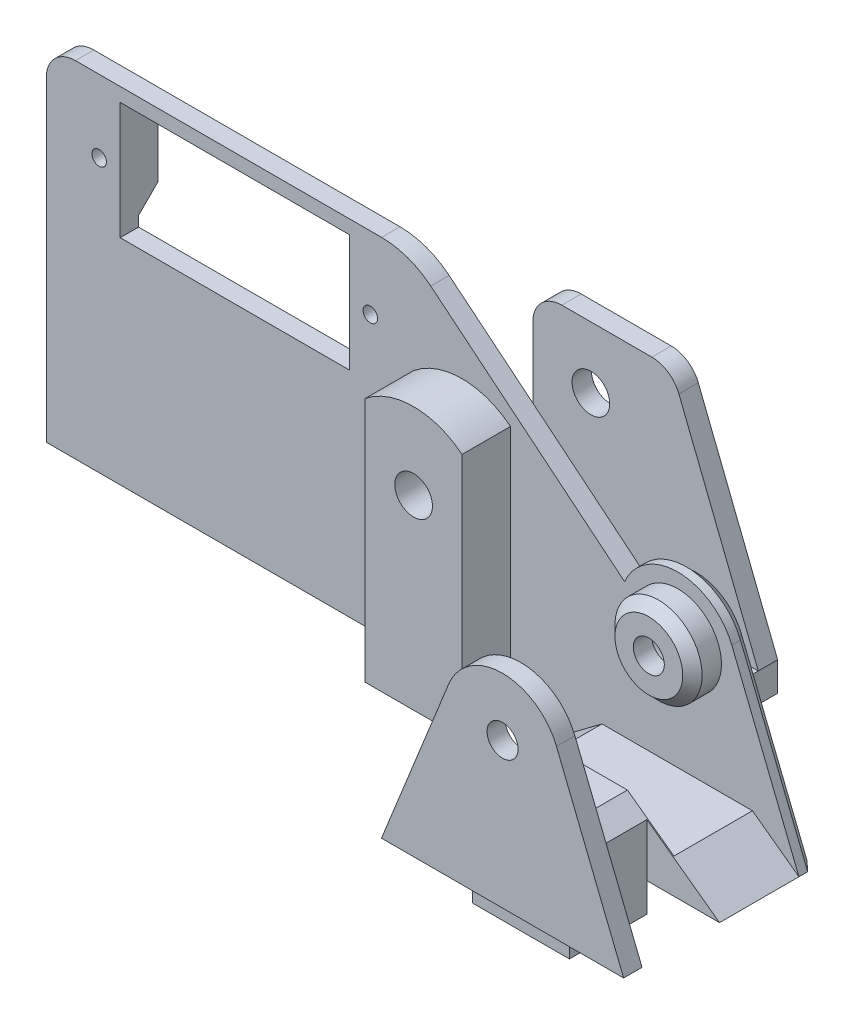
SolidWorks part; units mm, degrees
ref_plane "Alzado" through (0, 0, 0) normal (0, 0, 1) x (1, 0, 0)
ref_plane "Planta" through (0, 0, 0) normal (0, 1, 0) x (1, 0, 0)
ref_plane "Vista lateral" through (0, 0, 0) normal (1, 0, 0) x (0, 0, -1)
sketch "Croquis1" plane through (0, 0, 0) normal (0, 0, 1) x (1, 0, 0)
  line L0 (-12.5, -15) -> (-5.5666, 2.2389)
  line L1 (5.5666, 2.2389) -> (12.5, -15)
  line L2 (12.5, -15) -> (-12.5, -15)
  line L3 (0, 0) -> (0, -50000) construction
  circle A0 centre (0, 0) radius 1.6
  arc A1 (-5.5666, 2.2389) -> (5.5666, 2.2389) centre (0, 0) cw
  point P7 (0, -15)
  dimension "D1" = 3.2
  dimension "D2" = 6
  dimension "D3" = 15
  dimension "D4" = 25
extrude "Saliente-Extruir1" add sketch "Croquis1" along normal mid plane 20
sketch "Croquis2" plane through (0, 0, 0) normal (0, 0, 1) x (1, 0, 0)
  line L0 (12.5, -15) -> (5.5666, 2.2389) construction
  line L1 (-12.5, -15) -> (-7.5, 0)
  line L2 (12.5, -15) -> (7.5, 0)
  line L5 (-5.5666, 2.2389) -> (-12.5, -15) construction
  line L6 (-12.5, -15) -> (12.5, -15) construction
  line L7 (-12.5, -15) -> (-3.1648, -8)
  line L8 (-3.1648, -8) -> (2.8886, -8)
  line L9 (2.8886, -8) -> (12.5, -15)
  arc A0 (7.5, 0) -> (-7.5, 0) centre (0, 0) ccw
  dimension "D1" = 15
  dimension "D2" = 8
extrude "Cortar-Extruir1" cut sketch "Croquis2" against normal blind 8.1 and the other way blind 8.1
sketch "Croquis3" plane through (0, 0, 0) normal (0, 0, 1) x (1, 0, 0)
  line L0 (0, 0) -> (0, -50000) construction
  line L1 (-12.5, -15) -> (12.5, -15) construction
  line L2 (-5, 10.7975) -> (5, 10.7975)
  line L3 (-5, 10.7975) -> (-5, -15)
  line L4 (-5, -15) -> (5, -15)
  line L5 (5, 10.7975) -> (5, -15)
  line L6 (-5, 10.7975) -> (5, -15) construction
  line L7 (-5, -15) -> (5, 10.7975) construction
  point P3 (0, -2.1012)
  dimension "D1" = 10
extrude "Cortar-Extruir2" cut sketch "Croquis3" against normal blind 8 from surface flip side to cut starting at face at (1.6, 0, 8.1)
sketch "Croquis4" plane through (0, -15, 0) normal (0, -1, 0) x (1, 0, 0)
  line L1 (-5, 0.1) -> (5, 0.1)
  line L2 (-5, 0.1) -> (-5, 8.1)
  line L3 (-5, 8.1) -> (5, 8.1)
  line L4 (5, 0.1) -> (5, 8.1)
  line L5 (-5, 0.1) -> (5, 8.1) construction
  line L6 (-5, 8.1) -> (5, 0.1) construction
  point P0 (0, 0)
extrude "Saliente-Extruir3" add sketch "Croquis4" along normal blind 3
sketch "Croquis5" plane through (0, 0, 0) normal (1, 0, 0) x (0, 0, -1)
  line L0 (-8.1, -8) -> (8.1, -8) construction
  line L1 (0, -8) -> (8.1, -8)
  line L2 (0, -8) -> (0, -11.5)
  line L3 (0, -11.5) -> (8.1, -11.5)
  line L4 (8.1, -8) -> (8.1, -11.5)
  line L5 (0, -8) -> (8.1, -11.5) construction
  line L6 (0, -11.5) -> (8.1, -8) construction
  line L7 (8.1, -8) -> (8.1, -15) construction
  point P4 (4.05, -9.75)
extrude "Cortar-Extruir3" cut sketch "Croquis5" against normal through all both and the other way through all
sketch "Croquis6" plane through (0, 0, -8.1) normal (0, 0, 1) x (1, 0, 0)
  circle A0 centre (0, 0) radius 4.5
  circle A1 centre (0, 0) radius 1.6
  dimension "D1" = 9
extrude "Saliente-Extruir4" add sketch "Croquis6" along normal blind 3
chamfer "Chaflán1" distance 1 angle 45 1 edges at (4.5, 0, -5.1)
sketch "Croquis7" plane through (0, 0, -10) normal (0, 0, -1) x (-1, 0, 0)
  circle A0 centre (0, 0) radius 3.5
  dimension "D1" = 7
extrude "Cortar-Extruir4" cut sketch "Croquis7" against normal blind 3
sketch "Croquis8" plane through (0, 0, -10) normal (0, 0, -1) x (-1, 0, 0)
  line L1 (65.2, -15) -> (65.2, 20.6217)
  line L3 (5.5666, 2.2389) -> (12.5, -15)
  line L4 (5.5055, 2.3852) -> (25.5119, 18.8056)
  line L5 (30.5873, 20.6217) -> (65.2, 20.6217)
  line L7 (33.9223, 7.1) -> (57.5723, 7.1)
  line L8 (33.9223, 7.1) -> (33.9223, 19.2)
  line L10 (57.5723, 7.1) -> (57.5723, 19.2)
  line L13 (12.5, -15) -> (65.2, -15)
  line L14 (33.9223, 19.2) -> (57.5723, 19.2)
  arc A0 (5.5666, 2.2389) -> (-5.5666, 2.2389) centre (0, 0) ccw construction
  arc A1 (25.5119, 18.8056) -> (30.5873, 20.6217) centre (30.5873, 12.6217) cw
  circle A3 centre (59.7473, 13.15) radius 0.75
  circle A4 centre (31.7473, 13.15) radius 0.75
  arc A5 (5.5666, 2.2389) -> (5.5055, 2.3852) centre (0, 0) ccw
  circle A6 centre (22.2801, 4.2129) radius 1.945
  dimension "D2" = 8
  dimension "D1" = 1.5
extrude "Saliente-Extruir8" add sketch "Croquis8" against normal up to vertex (1.9 mm away) up to point (-5.5666, 2.2389, -8.1)
sketch "Croquis9" plane through (0, 0, -8.1) normal (0, 0, 1) x (1, 0, 0)
  line L1 (-27.2801, -15) -> (-17.2801, -15)
  line L2 (-27.2801, -15) -> (-27.2801, 10.371)
  line L4 (-17.2801, -15) -> (-17.2801, 10.371)
  line L5 (-27.2801, -15) -> (-16.1118, 27.9154) construction
  line L6 (-28.475, 28.0172) -> (-17.2801, -15) construction
  line L7 (-12.5, -15) -> (-65.2, -15) construction
  line L11 (-22.2801, 4.2129) -> (-22.2801, 50004.2129) construction
  arc A2 (-17.2801, 10.371) -> (-27.2801, 10.371) centre (-22.2801, 4.2129) ccw
  circle A3 centre (-22.2801, 4.2129) radius 1.945
  point P0 (-22.2801, 4.2129)
  dimension "D1" = 10
  dimension "D2" = 5
extrude "Saliente-Extruir9" add sketch "Croquis9" along normal blind 5
sketch "Croquis10" plane through (0, 0, -10) normal (0, 0, -1) x (-1, 0, 0)
  line L1 (5, -15) -> (28.2801, -15)
  line L2 (5, -15) -> (5, -12)
  line L3 (5, -12) -> (28.2801, -12)
  line L4 (28.2801, -15) -> (28.2801, -12)
  line L5 (65.2, -15) -> (-12.5, -15) construction
  dimension "D1" = 3
  dimension "D2" = 5
  dimension "D3" = 6
extrude "Saliente-Extruir10" add sketch "Croquis10" along normal blind 11.4
sketch "Croquis11" plane through (0, 0, -21.4) normal (0, 0, -1) x (-1, 0, 0)
  line L0 (28.2801, -15) -> (28.2801, 10.5661)
  line L1 (28.2801, 10.5661) -> (13.9465, 10.5661)
  line L2 (13.9465, 10.5661) -> (5, -12)
  line L3 (5, -12) -> (5, -15)
  line L4 (5, -15) -> (28.2801, -15)
  circle A0 centre (22.2801, 4.2129) radius 1.945
extrude "Saliente-Extruir11" add sketch "Croquis11" along normal blind 2
fillet "Redondeo1" radius 3 3 edges at (-13.9465, 10.5661, -22.4) (-28.2801, 10.5661, -22.4) (-65.2, 20.6217, -9.05)
sketch "Croquis12" plane through (0, 0, -10) normal (0, 0, -1) x (-1, 0, 0)
  line L0 (33.9223, 19.2) -> (33.9223, 7.1) construction
  line L1 (29.5723, 16.15) -> (33.9223, 16.15)
  line L2 (29.5723, 16.15) -> (29.5723, 10.15)
  line L3 (29.5723, 10.15) -> (33.9223, 10.15)
  line L4 (33.9223, 16.15) -> (33.9223, 10.15)
  line L5 (29.5723, 16.15) -> (33.9223, 10.15) construction
  line L6 (29.5723, 10.15) -> (33.9223, 16.15) construction
  line L7 (57.5723, 7.1) -> (57.5723, 19.2) construction
  line L8 (61.9223, 16.15) -> (57.5723, 16.15)
  line L9 (61.9223, 16.15) -> (61.9223, 10.15)
  line L10 (61.9223, 10.15) -> (57.5723, 10.15)
  line L11 (57.5723, 16.15) -> (57.5723, 10.15)
  line L12 (61.9223, 16.15) -> (57.5723, 10.15) construction
  line L13 (61.9223, 10.15) -> (57.5723, 16.15) construction
  circle A0 centre (31.7473, 13.15) radius 0.75
  circle A1 centre (59.7473, 13.15) radius 0.75
  circle A2 centre (31.7473, 13.15) radius 0.75 construction
  circle A3 centre (59.7473, 13.15) radius 0.75 construction
  point P0 (31.7473, 13.15)
  point P8 (59.7473, 13.15)
  dimension "D1" = 6
extrude "Saliente-Extruir12" add sketch "Croquis12" along normal blind 2
chamfer "Chaflán3" distance 2 angle 45 4 edges at (-31.7473, 16.15, -10) (-31.7473, 10.15, -10) (-59.7473, 10.15, -10) (-59.7473, 16.15, -10)
chamfer "Chaflán2" distance 1 angle 45 2 edges at (9.0333, -6.3806, -10) (0.0793, 5.9995, -10)
